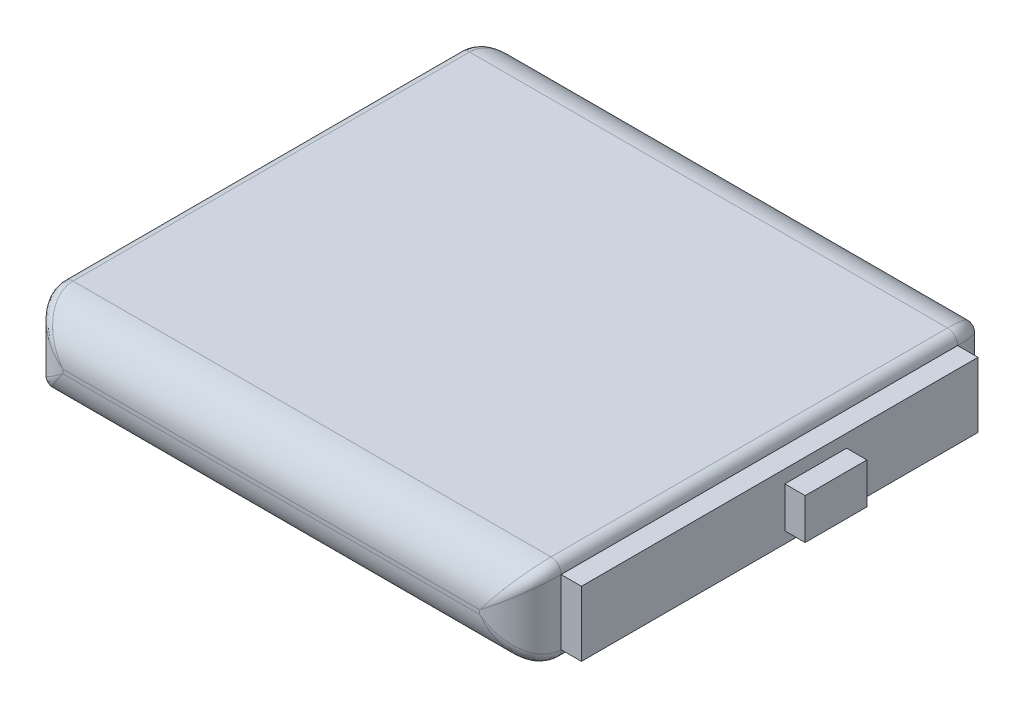
SolidWorks part; units mm, degrees
ref_plane "Front Plane" through (0, 0, 0) normal (0, 0, 1) x (1, 0, 0)
ref_plane "Top Plane" through (0, 0, 0) normal (0, 1, 0) x (1, 0, 0)
ref_plane "Right Plane" through (0, 0, 0) normal (1, 0, 0) x (0, 0, -1)
sketch "Sketch1" plane through (0, 0, 0) normal (0, 1, 0) x (1, 0, 0)
  line L1 (9.7444, -10.4273) -> (-14.7556, -10.4273)
  line L2 (9.7444, -10.4273) -> (9.7444, 13.0727)
  line L3 (9.7444, 13.0727) -> (-14.7556, 13.0727)
  line L4 (-14.7556, -10.4273) -> (-14.7556, 13.0727)
  dimension "D1" = 24.5
  dimension "D2" = 23.5
extrude "Boss-Extrude1" add sketch "Sketch1" along normal blind 4.2
fillet "Fillet1" radius 0.5 4 edges at (-14.7556, 0, -1.3227) (9.7444, 0, -1.3227) (9.7444, 4.2, -1.3227) (-14.7556, 4.2, -1.3227)
fillet "Fillet2" radius 2 16 edges at (-14.6092, 4.0536, 10.4273) (-14.7556, 2.1, 10.4273) (-14.6092, 0.1464, 10.4273) (9.598, 0.1464, 10.4273) (9.7444, 2.1, 10.4273) (9.598, 4.0536, 10.4273) (9.598, 4.0536, -13.0727) (9.7444, 2.1, -13.0727) (9.598, 0.1464, -13.0727) (-14.6092, 0.1464, -13.0727) (-14.7556, 2.1, -13.0727) (-14.6092, 4.0536, -13.0727) (-2.5056, 0, 10.4273) (-2.5056, 4.2, 10.4273) (-2.5056, 0, -13.0727) (-2.5056, 4.2, -13.0727)
sketch "Sketch2" plane through (9.7444, 0, 0) normal (1, 0, 0) x (0, 0, -1)
  line L1 (-8.4273, 3.7) -> (11.0727, 3.7)
  line L2 (-8.4273, 3.7) -> (-8.4273, 0.5)
  line L3 (-8.4273, 0.5) -> (11.0727, 0.5)
  line L4 (11.0727, 3.7) -> (11.0727, 0.5)
extrude "Boss-Extrude2" add sketch "Sketch2" along normal blind 1
sketch "Sketch3" plane through (10.7444, 0, 0) normal (1, 0, 0) x (0, 0, -1)
  line L0 (-8.4273, 3.7) -> (-8.4273, 0.5) construction
  line L1 (1.5727, 3.0608) -> (4.6109, 3.0608)
  line L2 (1.5727, 3.0608) -> (1.5727, 1.0608)
  line L3 (1.5727, 1.0608) -> (4.6109, 1.0608)
  line L4 (4.6109, 3.0608) -> (4.6109, 1.0608)
  dimension "D1" = 10
  dimension "D2" = 2
extrude "Boss-Extrude3" add sketch "Sketch3" along normal blind 1
